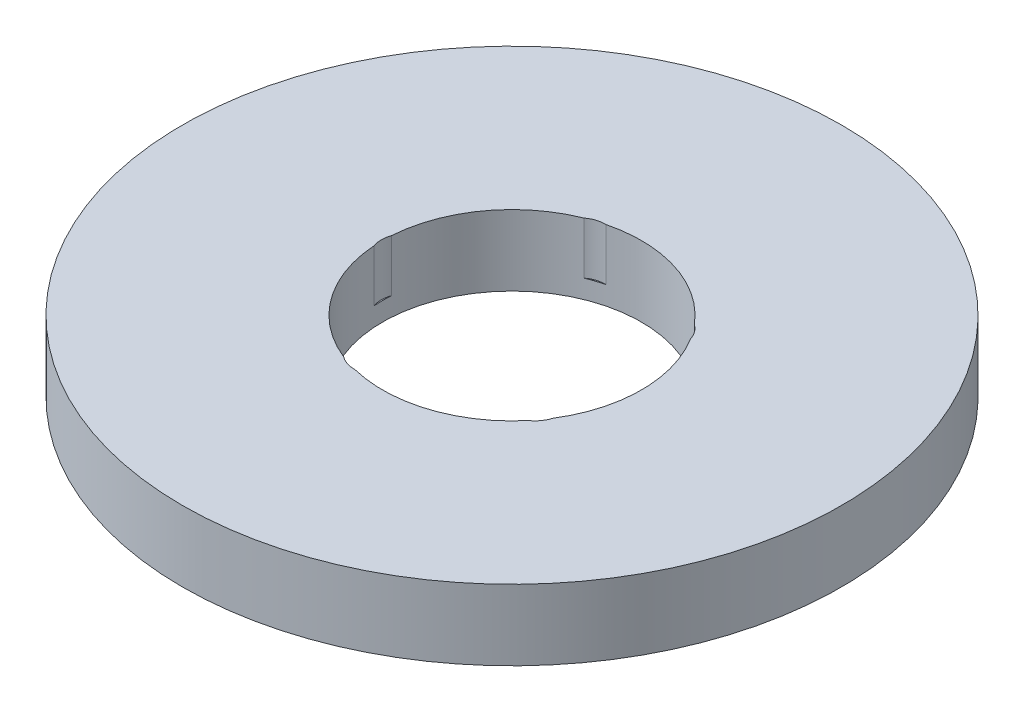
SolidWorks part; units mm, degrees
ref_plane "Front Plane" through (0, 0, 0) normal (0, 0, 1) x (1, 0, 0)
ref_plane "Top Plane" through (0, 0, 0) normal (0, 1, 0) x (1, 0, 0)
ref_plane "Right Plane" through (0, 0, 0) normal (1, 0, 0) x (0, 0, -1)
sketch "Sketch1" plane through (0, 0, 0) normal (0, 1, 0) x (1, 0, 0)
  circle A0 centre (0, 0) radius 70
  dimension "FLANGE_OD" = 140
extrude "Boss-Extrude1" add sketch "Sketch1" along normal blind 15
sketch "Sketch2" plane through (0, 0, 0) normal (0, 1, 0) x (1, 0, 0)
  circle A0 centre (0, 0) radius 27.5
  dimension "BORE_D" = 55
extrude "Cut-Extrude1" cut sketch "Sketch2" along normal through all
sketch "Sketch3" plane through (0, 15, 0) normal (0, 1, 0) x (1, 0, 0)
  circle A0 centre (0, 0) radius 22.1121 construction
  circle A1 centre (-22.1121, 0) radius 5.6427
  dimension "BOLT_D" = 11.2854
  dimension "BOLT_PCD" = 44.2242
extrude "Cut-Extrude2" cut sketch "Sketch3" against normal blind 11.0485
pattern_circular "CirPattern1" count 5 over 360 about axis through (0, 0, 0) along (0, 1, 0) of "Cut-Extrude2"
